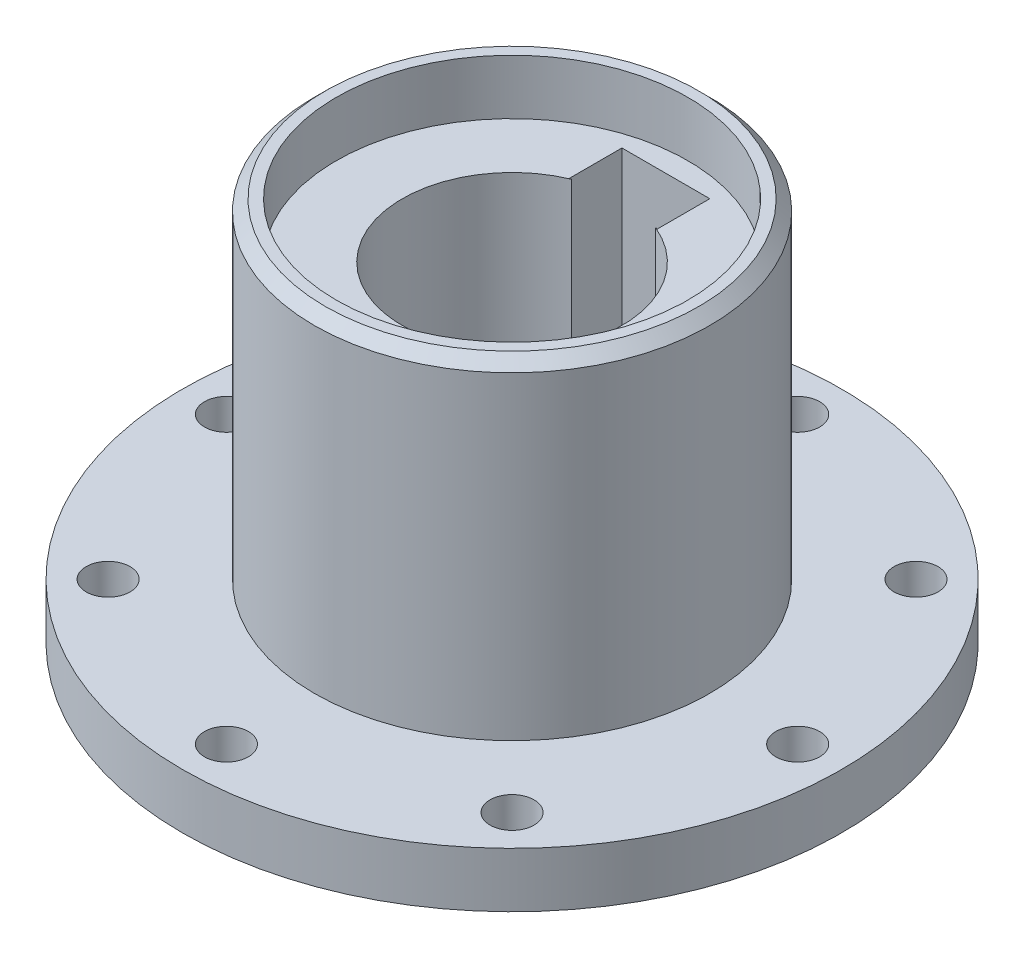
SolidWorks part; units mm, degrees
ref_plane "Спереди" through (0, 0, 0) normal (0, 0, 1) x (1, 0, 0)
ref_plane "Сверху" through (0, 0, 0) normal (0, 1, 0) x (1, 0, 0)
ref_plane "Справа" through (0, 0, 0) normal (1, 0, 0) x (0, 0, -1)
sketch "Эскиз1" plane through (0, 0, 0) normal (0, 0, 1) x (1, 0, 0)
  line L0 (0, 48.6541) -> (0, -58.6821) construction
  line L1 (-10, -11.7437) -> (-20.4, -11.7437)
  line L2 (-22, -10.1437) -> (-22, -6.7437)
  line L3 (-22, -6.7437) -> (-30, -6.7437)
  line L4 (-30, -6.7437) -> (-30, -1.7437)
  line L5 (-30, -1.7437) -> (-18, -1.7437)
  line L6 (-18, -1.7437) -> (-18, 27.2563)
  line L7 (-17, 28.2563) -> (-10, 28.2563)
  line L8 (-10, 28.2563) -> (-10, -11.7437)
  line L9 (-20.4, -11.7437) -> (-22, -10.1437)
  line L10 (-18, 27.2563) -> (-17, 28.2563)
  point P4 (-22, -10.37)
  point P5 (0, 0)
  point P10 (0, 0)
  point P12 (0, 0)
  point P13 (-10, -11.3919)
  point P16 (-22, -11.4388)
  point P17 (-22, -11.7437)
  point P18 (-22.0528, -9.9265)
  point P19 (0, 0)
  point P22 (-22, -11.7437)
  point P23 (-22, -11.7437)
  point P24 (-17.964, 24.2922)
  point P25 (-20.4979, -13.9757)
  point P26 (-14.6644, -17.7546)
  point P27 (-22, -9.7608)
  point P28 (-22, -7.1357)
  point P29 (-21.9453, -14.7521)
  point P30 (-18, 25.2667)
  point P31 (0, 0)
  point P32 (0, 0)
  dimension "D1" = 10
  dimension "D2" = 22
  dimension "D3" = 30
  dimension "D4" = 18
  dimension "D5" = 5
  dimension "D6" = 10
  dimension "D7" = 1.6
  dimension "D8" = 45
  dimension "D9" = 40
  dimension "D10" = 1
  dimension "D11" = 45
revolve "Повернуть1" add sketch "Эскиз1" angle 360 about L0
sketch "Эскиз2" plane through (0, 28.2563, 0) normal (0, 1, 0) x (1, 0, 0)
  circle A0 centre (0, 0) radius 16
extrude "Вырез-Вытянуть1" cut sketch "Эскиз2" against normal blind 5
sketch "Эскиз3" plane through (0, 23.2563, 0) normal (0, 1, 0) x (1, 0, 0)
  line L0 (-4, 9.2361) -> (4, 9.2361)
  line L1 (4, 14) -> (-4, 14)
  line L2 (-4, 14) -> (-4, 9.2361)
  line L3 (4, 14) -> (4, 9.2361)
  line L4 (0, 0) -> (0, -19.4387) construction
  line L5 (0, -19.4387) -> (0, 47.4387) construction
  circle A0 centre (0, 0) radius 10 construction
  point P4 (0, 14)
  dimension "D3" = 20
  dimension "D1" = 8
  dimension "D2" = 14
extrude "Вырез-Вытянуть2" cut sketch "Эскиз3" against normal blind 47
sketch "Эскиз4" plane through (0, -6.7437, 0) normal (0, -1, 0) x (1, 0, 0)
  line L0 (0, 26) -> (0, -26) construction
  circle A0 centre (0, 0) radius 26 construction
  circle A1 centre (0, 26) radius 2
  circle A2 centre (18.3848, 18.3848) radius 2
  circle A3 centre (26, 0) radius 2
  circle A4 centre (18.3848, -18.3848) radius 2
  circle A5 centre (0, -26) radius 2
  circle A6 centre (-18.3848, -18.3848) radius 2
  circle A7 centre (-26, 0) radius 2
  circle A8 centre (-18.3848, 18.3848) radius 2
  point P7 (0, 0)
  point P22 (0, 0)
  dimension "D1" = 8
  dimension "D2" = 4
extrude "Вырез-Вытянуть3" cut sketch "Эскиз4" against normal blind 47
